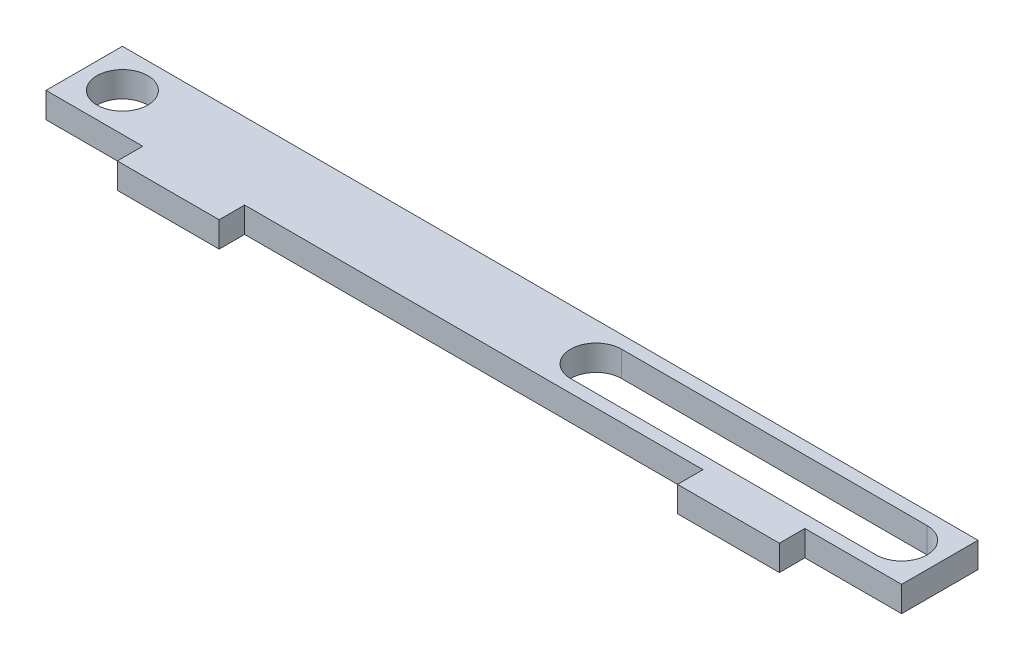
SolidWorks part; units mm, degrees
ref_plane "Front Plane" through (0, 0, 0) normal (0, 0, 1) x (1, 0, 0)
ref_plane "Top Plane" through (0, 0, 0) normal (0, 1, 0) x (1, 0, 0)
ref_plane "Right Plane" through (0, 0, 0) normal (1, 0, 0) x (0, 0, -1)
sketch "Sketch1" plane through (0, 0, 0) normal (0, 1, 0) x (1, 0, 0)
  line L0 (160.5, 7.5) -> (100.5, 7.5) construction
  line L1 (0, 0) -> (19, 0)
  line L2 (0, 0) -> (0, 15)
  line L3 (0, 15) -> (168, 15)
  line L4 (168, 0) -> (168, 15)
  line L5 (160.5, 2.5) -> (100.5, 2.5)
  line L6 (160.5, 12.5) -> (100.5, 12.5)
  line L7 (84, 15) -> (84, 0) construction
  line L9 (19, 0) -> (19, -5)
  line L10 (19, -5) -> (39, -5)
  line L11 (39, 0) -> (39, -5)
  line L12 (149, -5) -> (129, -5)
  line L13 (129, 0) -> (129, -5)
  line L15 (149, 0) -> (149, -5)
  line L16 (39, 0) -> (129, 0)
  line L17 (149, 0) -> (168, 0)
  circle A1 centre (7.5, 7.5) radius 5
  arc A2 (160.5, 2.5) -> (160.5, 12.5) centre (160.5, 7.5) ccw
  arc A3 (100.5, 12.5) -> (100.5, 2.5) centre (100.5, 7.5) ccw
  point P9 (130.5, 7.5)
  dimension "D3" = 10
  dimension "D7" = 5
  dimension "D1" = 168
  dimension "D2" = 15
  dimension "D4" = 7.5
  dimension "D5" = 7.5
  dimension "D6" = 7.5
  dimension "D8" = 60
  dimension "D9" = 5
  dimension "D10" = 20
  dimension "D11" = 45
extrude "Boss-Extrude1" add sketch "Sketch1" along normal blind 5
